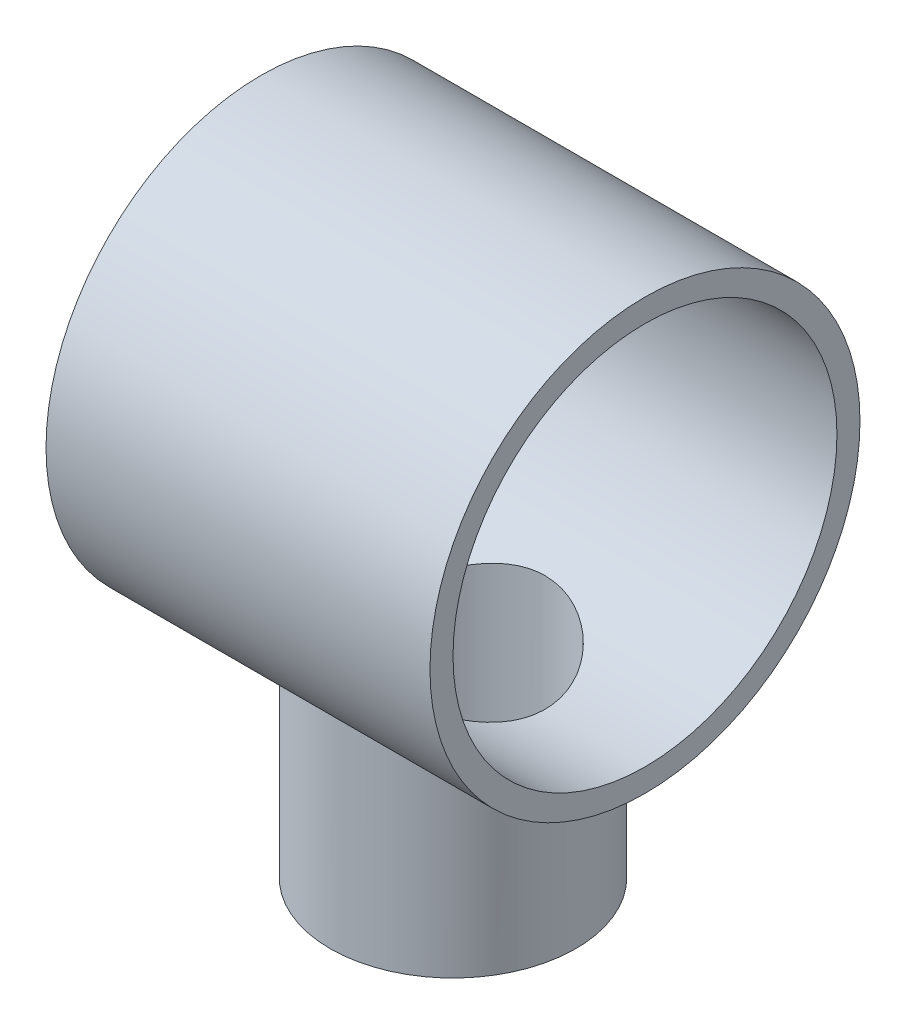
SolidWorks part; units mm, degrees
material "6061 合金"
ref_plane "前视基准面" through (0, 0, 0) normal (0, 0, 1) x (1, 0, 0)
ref_plane "上视基准面" through (0, 0, 0) normal (0, 1, 0) x (1, 0, 0)
ref_plane "右视基准面" through (0, 0, 0) normal (1, 0, 0) x (0, 0, -1)
sketch "草图1" plane through (0, 0, 0) normal (0, 1, 0) x (1, 0, 0)
  circle A0 centre (0, 0) radius 8
  circle A1 centre (0, 0) radius 6
  dimension "D1" = 16
  dimension "D2" = 2
extrude "凸台-拉伸1" add sketch "草图1" along normal blind 10 and the other way blind 10
sketch "草图2" plane through (0, 0, 0) normal (1, 0, 0) x (0, 0, -1)
  line L0 (0, 15) -> (0, 10) construction
  line L1 (6, 10) -> (-6, 10) construction
  circle A0 centre (0, 15) radius 12.5
  circle A1 centre (0, 15) radius 14
  dimension "D1" = 25
  dimension "D2" = 1.5
  dimension "D3" = 5
extrude "凸台-拉伸2" add sketch "草图2" along normal mid plane 25
sketch "草图3" plane through (0, 0, 0) normal (1, 0, 0) x (0, 0, -1)
  circle A0 centre (0, 15) radius 12.5
extrude "切除-拉伸1" cut sketch "草图3" against normal through all both and the other way through all
sketch "草图4" plane through (0, -10, 0) normal (0, -1, 0) x (1, 0, 0)
  circle M1 centre (0, 0) radius 6
extrude "切除-拉伸2" cut sketch "草图4" against normal blind 20 contours M1 region at (0, -10, 0)
